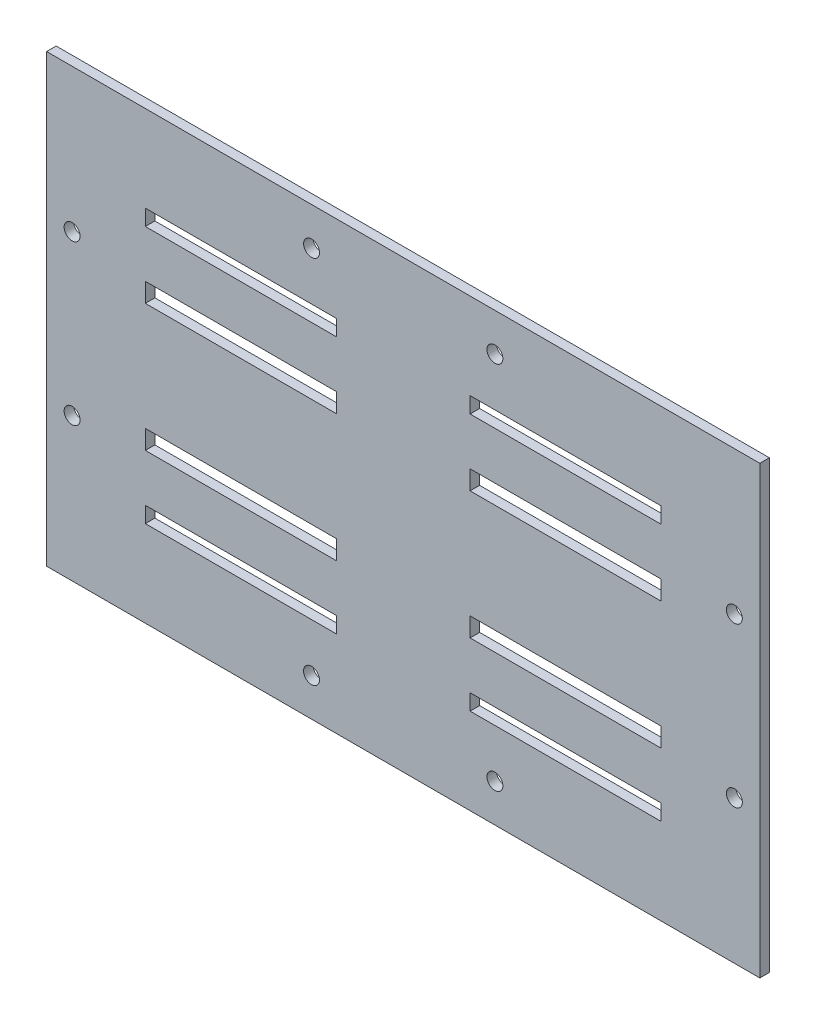
SolidWorks part; units mm, degrees
ref_plane "Front" through (0, 0, 0) normal (0, 0, 1) x (1, 0, 0)
ref_plane "Top" through (0, 0, 0) normal (0, 1, 0) x (1, 0, 0)
ref_plane "Right" through (0, 0, 0) normal (1, 0, 0) x (0, 0, -1)
sketch "草图2" plane through (0, 0, 0) normal (0, 0, 1) x (1, 0, 0)
  line L1 (-100, -70) -> (100, -70)
  line L2 (-100, -70) -> (-100, 70)
  line L3 (-100, 70) -> (100, 70)
  line L4 (100, -70) -> (100, 70)
  line L5 (-100, -70) -> (100, 70) construction
  line L6 (-100, 70) -> (100, -70) construction
  point P0 (0, 0)
  dimension "D1" = 140
  dimension "D2" = 200
extrude "凸台-拉伸1" add sketch "草图2" along normal blind 3
sketch "草图4" plane through (0, 0, 3) normal (0, 0, 1) x (1, 0, 0)
  line L0 (-100, 0) -> (100, 0) construction
  line L1 (-100, 70) -> (-100, -70) construction
  line L2 (100, -70) -> (100, 70) construction
  line L4 (21, 23) -> (81, 23)
  line L5 (21, 23) -> (21, 17)
  line L6 (21, 17) -> (81, 17)
  line L7 (81, 23) -> (81, 17)
  line L8 (21, 23) -> (81, 17) construction
  line L9 (21, 17) -> (81, 23) construction
  line L10 (21, -23) -> (81, -23)
  line L11 (21, -23) -> (21, -17)
  line L12 (21, -17) -> (81, -17)
  line L13 (81, -23) -> (81, -17)
  line L14 (21, -23) -> (81, -17) construction
  line L15 (21, -17) -> (81, -23) construction
  point P6 (51, 20)
  point P11 (51, -20)
  dimension "D1" = 34
  dimension "D2" = 6
  dimension "D3" = 6
  dimension "D4" = 17
  dimension "D5" = 60
  dimension "D6" = 19
extrude "切除-拉伸2" cut sketch "草图4" against normal blind 10
sketch "草图5" plane through (0, 0, 0) normal (0, 0, -1) x (-1, 0, 0)
  line L0 (-21, 17) -> (-21, 23) construction
  line L1 (-81, 37.9088) -> (-21, 37.9088)
  line L2 (-81, 37.9088) -> (-81, 42.9088)
  line L3 (-81, 42.9088) -> (-21, 42.9088)
  line L4 (-21, 37.9088) -> (-21, 42.9088)
  line L5 (-81, 37.9088) -> (-21, 42.9088) construction
  line L6 (-81, 42.9088) -> (-21, 37.9088) construction
  line L7 (-81, 23) -> (-81, 17) construction
  point P0 (-51, 40.4088)
  dimension "D1" = 5
extrude "切除-拉伸3" cut sketch "草图5" against normal blind 6
mirror "镜向1" about plane through (0, 0, 0) normal (0, 1, 0) of "切除-拉伸3"
ref_plane "基准面1" through (0, 0, 0) normal (-1, 0, 0) x (0, 0, 1)
sketch "草图6" plane through (0, 0, 3) normal (0, 0, 1) x (1, 0, 0)
  circle A0 centre (-28.8, 58.1086) radius 2.5 construction
  circle A1 centre (-28.8, 58.1086) radius 2.5
  circle A2 centre (-28.8, -58.1086) radius 2.5 construction
  circle A3 centre (28.8, -58.1086) radius 2.5 construction
  circle A4 centre (28.8, 58.1086) radius 2.5 construction
  circle A5 centre (-28.8, -58.1086) radius 2.5
  circle A6 centre (28.8, -58.1086) radius 2.5
  circle A7 centre (28.8, 58.1086) radius 2.5
extrude "切除-拉伸4" cut sketch "草图6" against normal blind 5
sketch "草图7" plane through (0, 0, 3) normal (0, 0, 1) x (1, 0, 0)
  point P0 (-100, -70)
sketch "草图9" plane through (100, 0, 0) normal (1, 0, 0) x (0, 0, -1)
  line L4 (0, -70) -> (0, 70)
  line L5 (0, 70) -> (-3, 70)
  line L6 (0, 70) -> (-3, 70)
  line L7 (-3, -70) -> (0, -70)
  line L8 (0, -70) -> (0, 70)
  line L9 (-3, 70) -> (-3, -70)
  line L10 (-3, 70) -> (-3, -70)
  line L11 (-3, -70) -> (0, -70)
  dimension "D1" = 0
extrude "凸台-拉伸2" add sketch "草图9" along normal blind 12
sketch "草图10" plane through (-100, 0, 0) normal (-1, 0, 0) x (0, 0, 1)
  line L4 (0, 70) -> (0, -70)
  line L5 (0, -70) -> (3, -70)
  line L6 (3, -70) -> (3, 70)
  line L7 (0, 70) -> (0, -70)
  line L8 (3, 70) -> (0, 70)
  line L9 (0, -70) -> (3, -70)
  line L10 (3, -70) -> (3, 70)
  line L11 (3, 70) -> (0, 70)
  dimension "D1" = 0
extrude "凸台-拉伸3" add sketch "草图10" along normal blind 12
sketch "草图11" plane through (0, 0, 3) normal (0, 0, 1) x (1, 0, 0)
  line L0 (112, 70) -> (112, -70) construction
  circle A0 centre (104, 25) radius 2.5
  circle A1 centre (104, -25) radius 2.5
  point P4 (0, 0)
  dimension "D4" = 5
  dimension "D1" = 25
  dimension "D2" = 25
  dimension "D3" = 8
extrude "切除-拉伸5" cut sketch "草图11" against normal blind 12
mirror "镜向2" about plane through (0, 0, 0) normal (1, 0, 0) of "切除-拉伸5", "镜向1", "切除-拉伸2", "切除-拉伸3"
